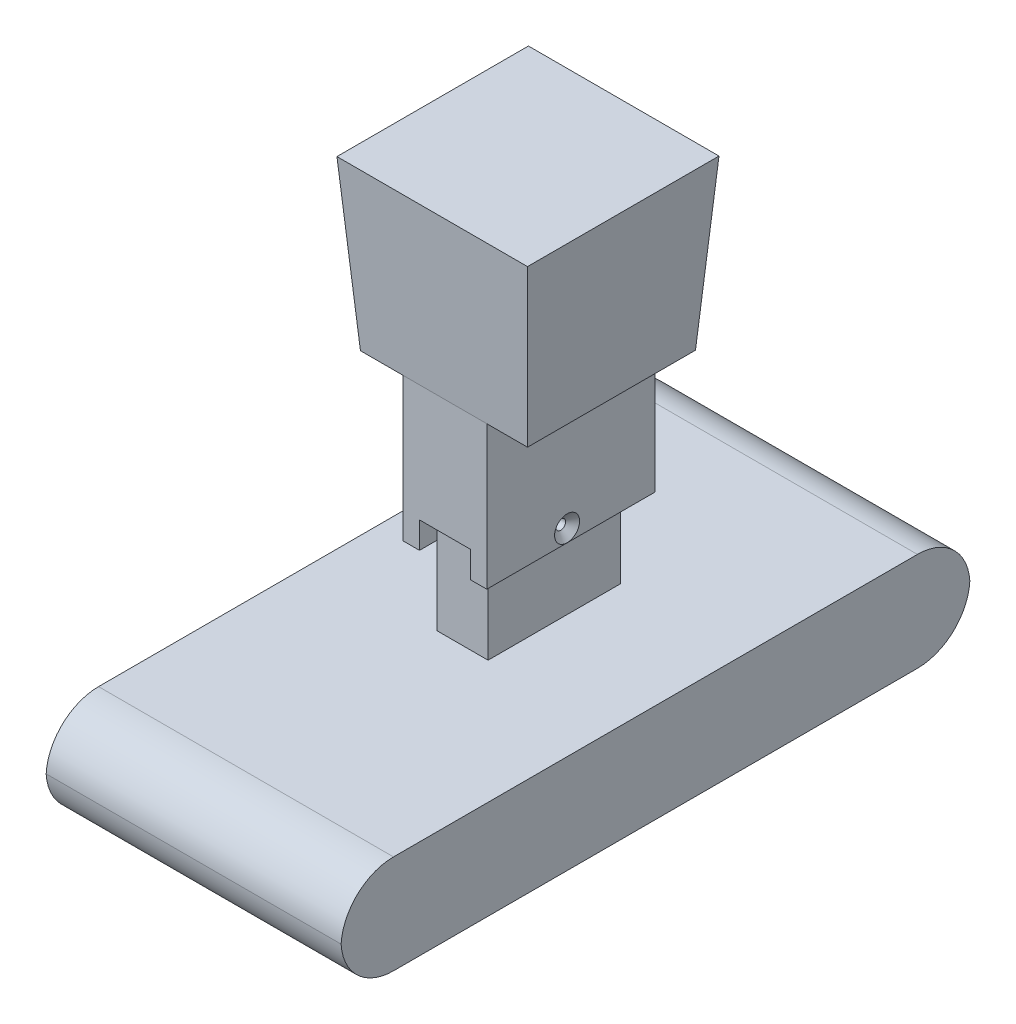
SolidWorks part; units mm, degrees
ref_plane "Front Plane" through (0, 0, 0) normal (0, 0, 1) x (1, 0, 0)
ref_plane "Top Plane" through (0, 0, 0) normal (0, 1, 0) x (1, 0, 0)
ref_plane "Right Plane" through (0, 0, 0) normal (1, 0, 0) x (0, 0, -1)
sketch "Sketch5" plane through (0, 0, 0) normal (0, 0, 1) x (1, 0, 0)
  line L1 (-120.2339, 76.1959) -> (-100.0242, 76.1959)
  line L2 (-120.2339, 76.1959) -> (-120.2339, 55.8497)
  line L3 (-120.2339, 55.8497) -> (-100.0242, 55.8497)
  line L4 (-100.0242, 76.1959) -> (-100.0242, 55.8497)
extrude "Boss-Extrude3" add sketch "Sketch5" along normal blind 20.32
draft "Draft4" type of draft neutral plane draft angle 4 faces to draft 3 face at (-100.0242, 66.0228, 10.16) face at (-120.2339, 66.0228, 10.16) face at (-110.129, 66.0228, 20.32) neutral plane through (-120.2339, 55.8497, 20.32) neutral plane normal (0, -1, 0) parameters "D1"=4
draft "Draft5" type of draft neutral plane draft angle 4 faces to draft 1 face at (-110.129, 66.0228, 0) neutral plane through (-120.2339, 55.8497, 20.32) neutral plane normal (0, -1, 0) parameters "D1"=4
sketch "Sketch6" plane through (0, 0, 0) normal (0, 0, 1) x (1, 0, 0)
  line L0 (-120.2339, 55.8497) -> (-100.0242, 55.8497) construction
  line L2 (-115.0844, 55.8497) -> (-104.9502, 55.8497)
  line L3 (-115.0844, 55.8497) -> (-115.0844, 38.5086)
  line L4 (-115.0844, 38.5086) -> (-104.9502, 38.5086)
  line L5 (-104.9502, 55.8497) -> (-104.9502, 38.5086)
extrude "Boss-Extrude4" add sketch "Sketch6" along normal blind 20.32
sketch "Sketch7" plane through (0, 0, 0) normal (0, 0, 1) x (1, 0, 0)
  line L0 (-115.0844, 38.5086) -> (-104.9502, 38.5086) construction
  line L1 (-106.9383, 38.5086) -> (-113.0894, 38.5086)
  line L2 (-106.9383, 38.5086) -> (-106.9383, 26.2065)
  line L3 (-106.9383, 26.2065) -> (-113.0894, 26.2065)
  line L4 (-113.0894, 38.5086) -> (-113.0894, 26.2065)
extrude "Boss-Extrude5" add sketch "Sketch7" along normal blind 20.32
sketch "Sketch8" plane through (0, 0, 0) normal (0, 0, -1) x (-1, 0, 0)
  line L0 (106.9383, 38.5086) -> (106.9383, 41.7033)
  line L2 (113.0894, 41.7033) -> (106.9383, 41.7033)
  line L3 (113.0894, 38.5086) -> (113.0894, 41.7033)
  line L4 (106.9383, 38.5086) -> (106.9383, 41.7033)
  line L5 (113.0894, 41.7033) -> (106.9383, 41.7033)
  line M5 (106.9383, 38.5086) -> (106.9383, 26.2065)
  line M6 (106.9383, 26.2065) -> (113.0894, 26.2065)
  line M7 (113.0894, 26.2065) -> (113.0894, 38.5086)
extrude "Cut-Extrude1" cut sketch "Sketch8" against normal blind 20.32 contours L3 L2 L0 M7 M5 M6 region at (-110.0138, 33.9549, 0)
sketch "Sketch9" plane through (0, 41.7033, 0) normal (0, -1, 0) x (1, 0, 0)
  line L0 (-113.0894, 20.32) -> (-113.0894, 0) construction
  line L1 (-113.0894, 18.1772) -> (-106.9383, 18.1772)
  line L2 (-113.0894, 18.1772) -> (-113.0894, 2.1382)
  line L3 (-113.0894, 2.1382) -> (-106.9383, 2.1382)
  line L4 (-106.9383, 18.1772) -> (-106.9383, 2.1382)
  line L5 (-106.9383, 20.32) -> (-106.9383, 0) construction
extrude "Boss-Extrude8" add sketch "Sketch9" along normal blind 12.7
hole_wizard "#0-80 Tapped Hole1" positions "Sketch23" profile "Sketch19" tap size "#0-80" standard "ANSI Inch"
sketch "Sketch23" plane through (-104.9502, 0, 0) normal (1, 0, 0) x (0, 0, -1)
  point P0 (-10.6062, 40.0347)
sketch "Sketch19" plane through (-104.9502, 40.0347, 10.6062) normal (0, 1, 0) x (0, 0, -1)
  line L0 (0, 0) -> (0, 4.3584)
  line L1 (0, 4.3584) -> (0.5956, 4.0005)
  line L2 (0.5956, 4.0005) -> (0.5956, 0.7683)
  line L3 (0.5956, 0.7683) -> (1.5113, 0)
  line L5 (1.5113, 0) -> (0, 0)
  line L6 (-0.5956, 0.7683) -> (-1.5113, 0) construction
  line L10 (0, 4.3584) -> (-0.5956, 4.0005) construction
  line L11 (0, -6.35) -> (0, 107.95) construction
  dimension "Tap Drill Dia." = 1.1913
  dimension "Tap Drill Depth" = 4.0005
  dimension "Near C'Sink Dia." = 3.0226
  dimension "Near C'Sink Angle" = 100
  dimension "Drill Angle" = 118
cosmetic thread "Hole Thread1" parameters "D1"=3.048, "D2"=1.524
hole_wizard "#0-80 Tapped Hole3" positions "Sketch26" profile "Sketch27" tap size "#0-80" standard "ANSI Inch"
sketch "Sketch26" plane through (-115.0844, 0, 0) normal (-1, 0, 0) x (0, 0, 1)
  point P0 (10.6106, 40.0031)
sketch "Sketch27" plane through (-115.0844, 40.0031, 10.6106) normal (0, 1, 0) x (0, 0, 1)
  line L0 (0, 0) -> (0, 4.4219)
  line L1 (0, 4.4219) -> (0.5956, 4.064)
  line L2 (0.5956, 4.064) -> (0.5956, 0.7683)
  line L3 (0.5956, 0.7683) -> (1.5113, 0)
  line L5 (1.5113, 0) -> (0, 0)
  line L6 (-0.5956, 0.7683) -> (-1.5113, 0) construction
  line L10 (0, 4.4219) -> (-0.5956, 4.064) construction
  line L11 (0, -6.35) -> (0, 107.95) construction
  dimension "Tap Drill Dia." = 1.1913
  dimension "Tap Drill Depth" = 4.064
  dimension "Near C'Sink Dia." = 3.0226
  dimension "Near C'Sink Angle" = 100
  dimension "Drill Angle" = 118
cosmetic thread "Hole Thread3" parameters "D1"=3.048, "D2"=1.524
sketch "Sketch28" plane through (0, 29.0033, 0) normal (0, -1, 0) x (-1, 0, 0)
  line L1 (92.0525, 25.2337) -> (127.7353, 25.2337)
  line L2 (92.0525, 25.2337) -> (92.0525, -50.8538)
  line L3 (92.0525, -50.8538) -> (127.7353, -50.8538)
  line L4 (127.7353, 25.2337) -> (127.7353, -50.8538)
extrude "Boss-Extrude13" add sketch "Sketch28" along normal blind 11.938
fillet "Fillet5" radius 6.35 2 edges at (-109.8939, 17.0653, -25.2337) (-109.8939, 29.0033, -25.2337)
fillet "Fillet6" radius 6.35 2 edges at (-109.8939, 17.0653, 50.8538) (-109.8939, 29.0033, 50.8538)
